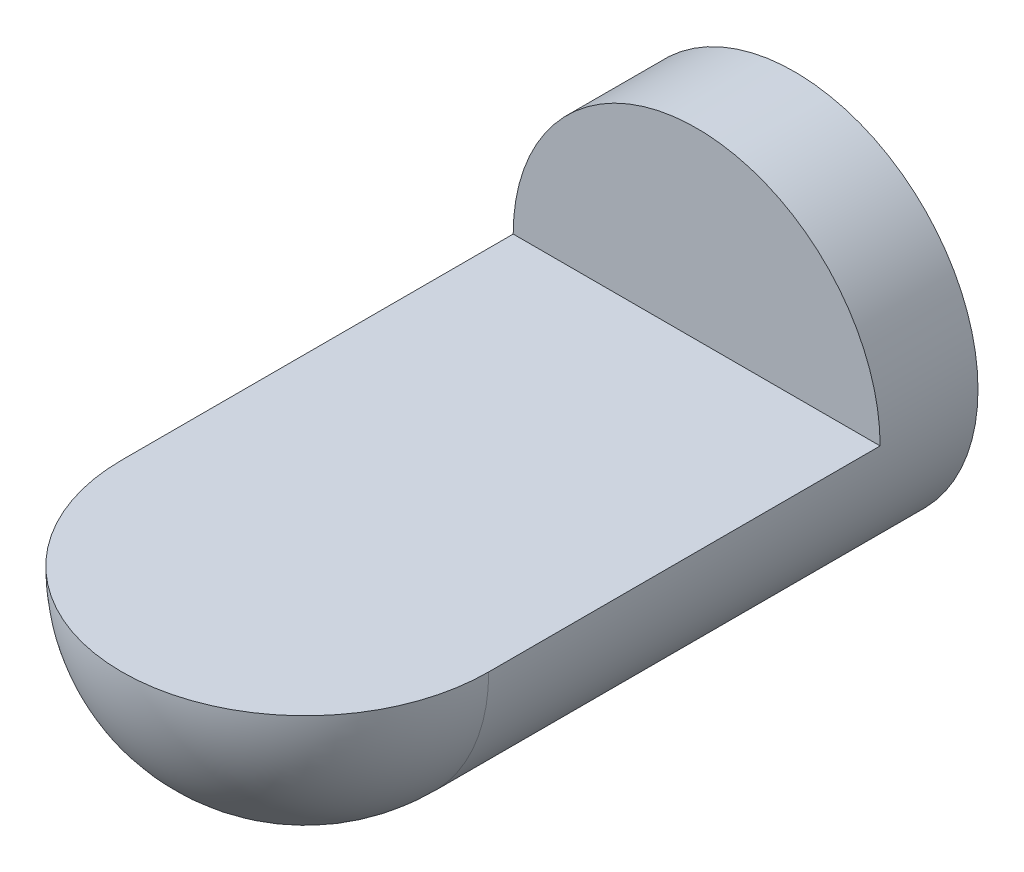
SolidWorks part; units mm, degrees
ref_plane "Front Plane" through (0, 0, 0) normal (0, 0, 1) x (1, 0, 0)
ref_plane "Top Plane" through (0, 0, 0) normal (0, 1, 0) x (1, 0, 0)
ref_plane "Right Plane" through (0, 0, 0) normal (1, 0, 0) x (0, 0, -1)
sketch "Sketch1" plane through (0, 0, 0) normal (1, 0, 0) x (0, 0, -1)
  line L0 (-146.9091, 0) -> (313.5945, 0) construction
  line L1 (200, 0) -> (-75, 0)
  line L2 (200, 0) -> (200, 75)
  line L3 (0, 75) -> (200, 75)
  arc A0 (-75, 0) -> (0, 75) centre (0, 0) cw
  dimension "D1" = 75
  dimension "D2" = 200
revolve "Revolve1" add sketch "Sketch1" angle 360 about L0
sketch "Sketch2" plane through (0, 0, 0) normal (1, 0, 0) x (0, 0, -1)
  line L0 (-88.0407, 0) -> (120.4455, 0) construction
  line L1 (160, 0) -> (160, 75)
  line L2 (200, 75) -> (0, 75) construction
  line L3 (160, 0) -> (-75, 0)
  line L4 (160, 75) -> (0, 75)
  line L5 (200, -75) -> (200, 75) construction
  arc A0 (0, 75) -> (0, -75) centre (0, 0) ccw construction
  arc A1 (-75, 0) -> (0, 75) centre (0, 0) cw
  dimension "D1" = 40
extrude "Cut-Extrude1" cut sketch "Sketch2" along normal through all and the other way through all
ref_axis "Axis1" through (0, 82.5, 0) along (0, -1, 0)
equation "\"link5_diameter\"=150"
equation "\"D1@Sketch1\"=\"link5_diameter\"/2"
equation "\"link5_length\"=200"
equation "\"D2@Sketch1\"=\"link5_length\""
equation "\"base_link_length\"=150"
equation "\"link1_diameter\"=150"
equation "\"link1_length\"=150"
equation "\"link2_diameter\"=150"
equation "\"link2_length\"=300"
equation "\"link3_diameter\"=150"
equation "\"link3_length\"=150"
equation "\"link4_diameter\"=150"
equation "\"link4_length\"=150"
equation "\"end_effector_diameter\"=150"
equation "\"end_effector_length\"=150"
equation "\"base_link_diameterA\"=200"
equation "\"base_link_diameterB\"=150"
equation "\"base_link_lengthA\"=50"
equation "\"base_link_diameter\"=75"
